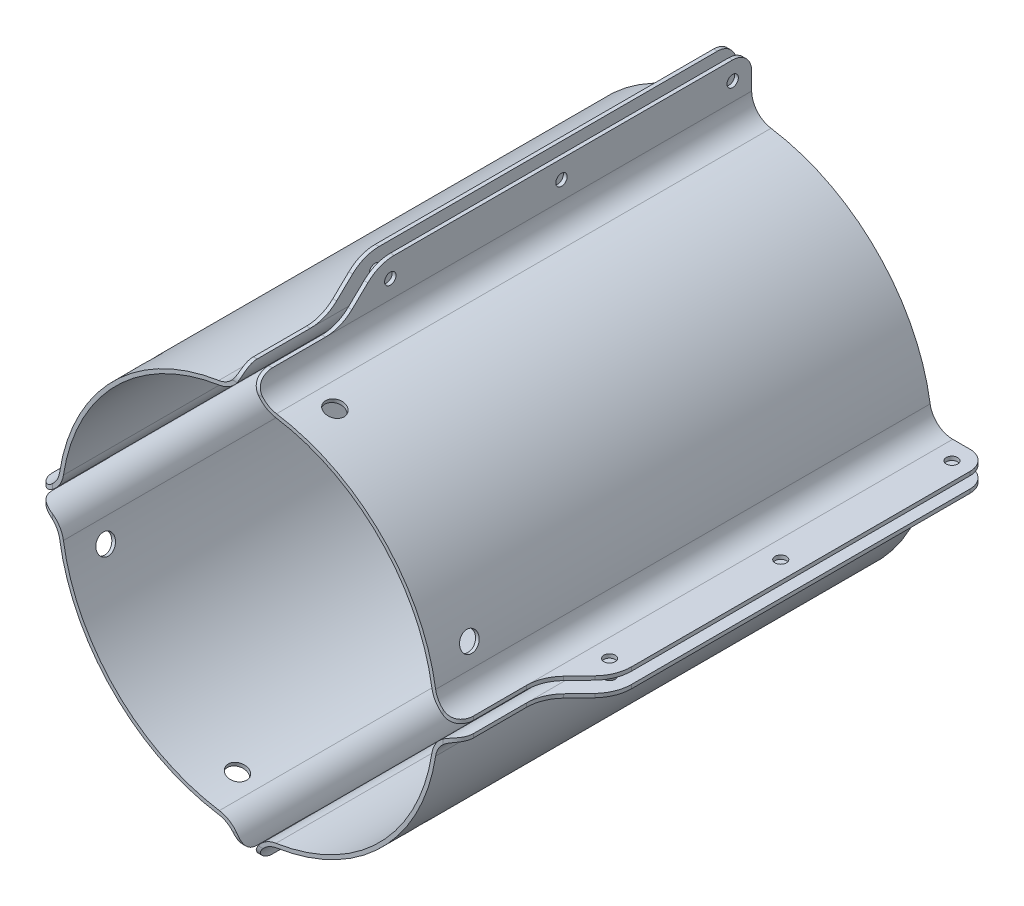
SolidWorks part; units mm, degrees
ref_plane "Спереди" through (0, 0, 0) normal (0, 0, 1) x (1, 0, 0)
ref_plane "Сверху" through (0, 0, 0) normal (0, 1, 0) x (1, 0, 0)
ref_plane "Справа" through (0, 0, 0) normal (1, 0, 0) x (0, 0, -1)
sketch "Эскиз1" plane through (0, 0, 0) normal (0, 0, 1) x (1, 0, 0)
  line L0 (0, 0) -> (0, 63.1749) construction
  line L1 (2.5, 55.3512) -> (2.5, 64.9375)
  line L2 (1.5, 64.9375) -> (1.5, 55.3512)
  line L3 (1.5, 64.9375) -> (2.5, 64.9375)
  line L4 (-1.5, 64.9375) -> (-2.5, 64.9375)
  line L5 (-1.5, 64.9375) -> (-1.5, 55.3512)
  line L6 (-2.5, 55.3512) -> (-2.5, 64.9375)
  line L7 (55.3512, -2.5) -> (64.9375, -2.5)
  line L8 (64.9375, -1.5) -> (55.3512, -1.5)
  line L9 (64.9375, -1.5) -> (64.9375, -2.5)
  line L10 (64.9375, 1.5) -> (64.9375, 2.5)
  line L11 (64.9375, 1.5) -> (55.3512, 1.5)
  line L12 (55.3512, 2.5) -> (64.9375, 2.5)
  line L13 (-2.5, -55.3512) -> (-2.5, -64.9375)
  line L14 (-1.5, -64.9375) -> (-1.5, -55.3512)
  line L15 (-1.5, -64.9375) -> (-2.5, -64.9375)
  line L16 (1.5, -64.9375) -> (2.5, -64.9375)
  line L17 (1.5, -64.9375) -> (1.5, -55.3512)
  line L18 (2.5, -55.3512) -> (2.5, -64.9375)
  line L19 (-55.3512, 2.5) -> (-64.9375, 2.5)
  line L20 (-64.9375, 1.5) -> (-55.3512, 1.5)
  line L21 (-64.9375, 1.5) -> (-64.9375, 2.5)
  line L22 (-64.9375, -1.5) -> (-64.9375, -2.5)
  line L23 (-64.9375, -1.5) -> (-55.3512, -1.5)
  line L24 (-55.3512, -2.5) -> (-64.9375, -2.5)
  arc A0 (-7.5893, 49.4207) -> (-49.4207, 7.5893) centre (0, 0) ccw
  arc A1 (-7.4375, 48.4323) -> (-48.4323, 7.4375) centre (0, 0) ccw
  arc A2 (-7.5893, 49.4207) -> (-2.5, 55.3512) centre (-8.5, 55.3512) ccw
  arc A3 (-7.4375, 48.4323) -> (-1.5, 55.3512) centre (-8.5, 55.3512) ccw
  arc A4 (7.4375, 48.4323) -> (1.5, 55.3512) centre (8.5, 55.3512) cw
  arc A5 (7.5893, 49.4207) -> (2.5, 55.3512) centre (8.5, 55.3512) cw
  arc A6 (49.4207, 7.5893) -> (55.3512, 2.5) centre (55.3512, 8.5) ccw
  arc A7 (48.4323, 7.4375) -> (55.3512, 1.5) centre (55.3512, 8.5) ccw
  arc A8 (48.4323, -7.4375) -> (55.3512, -1.5) centre (55.3512, -8.5) cw
  arc A9 (49.4207, -7.5893) -> (55.3512, -2.5) centre (55.3512, -8.5) cw
  arc A10 (7.5893, -49.4207) -> (2.5, -55.3512) centre (8.5, -55.3512) ccw
  arc A11 (7.4375, -48.4323) -> (1.5, -55.3512) centre (8.5, -55.3512) ccw
  arc A12 (-7.4375, -48.4323) -> (-1.5, -55.3512) centre (-8.5, -55.3512) cw
  arc A13 (-7.5893, -49.4207) -> (-2.5, -55.3512) centre (-8.5, -55.3512) cw
  arc A14 (-49.4207, -7.5893) -> (-55.3512, -2.5) centre (-55.3512, -8.5) ccw
  arc A15 (-48.4323, -7.4375) -> (-55.3512, -1.5) centre (-55.3512, -8.5) ccw
  arc A16 (-48.4323, 7.4375) -> (-55.3512, 1.5) centre (-55.3512, 8.5) cw
  arc A17 (-49.4207, 7.5893) -> (-55.3512, 2.5) centre (-55.3512, 8.5) cw
  arc A18 (-49.4207, -7.5893) -> (-7.5893, -49.4207) centre (0, 0) ccw
  arc A19 (-48.4323, -7.4375) -> (-7.4375, -48.4323) centre (0, 0) ccw
  arc A20 (7.4375, -48.4323) -> (48.4323, -7.4375) centre (0, 0) ccw
  arc A21 (7.5893, -49.4207) -> (49.4207, -7.5893) centre (0, 0) ccw
  arc A22 (49.4207, 7.5893) -> (7.5893, 49.4207) centre (0, 0) ccw
  arc A23 (48.4323, 7.4375) -> (7.4375, 48.4323) centre (0, 0) ccw
  point P13 (-2.5, 49.9375)
  point P16 (-1.5, 48.977)
  point P19 (1.5, 48.977)
  point P22 (2.5, 49.9375)
  point P74 (0, 0)
  dimension "D1" = 100
  dimension "D6" = 6
  dimension "D7" = 7
  dimension "D8" = 7
  dimension "D9" = 6
  dimension "D2" = 1
  dimension "D3" = 15
  dimension "D4" = 5
  dimension "D5" = 1
  dimension "D10" = 4
extrude "Бобышка-Вытянуть1" add sketch "Эскиз1" along normal blind 130
sketch "Эскиз2" plane through (2.5, 0, 0) normal (1, 0, 0) x (0, 0, -1)
  line L1 (0, 55.3512) -> (0, 64.9375) construction
  line L2 (-130, 64.9375) -> (-98, 64.9375)
  line L3 (-130, 64.9375) -> (0, 64.9375) construction
  line L4 (-98, 64.9375) -> (-108, 55.3512)
  line L5 (-130, 55.3512) -> (0, 55.3512) construction
  line L6 (-108, 55.3512) -> (-130, 55.3512)
  line L7 (-130, 64.9375) -> (-130, 55.3512)
  circle A0 centre (-5, 60.1443) radius 1.5
  circle A1 centre (-50, 60.1443) radius 1.5
  circle A2 centre (-95, 60.1443) radius 1.5
  point P12 (0, 60.1443)
  dimension "D3" = 3
  dimension "D1" = 45
  dimension "D2" = 45
  dimension "D4" = 5
  dimension "D5" = 13
  dimension "D6" = 3
extrude "Вырез-Вытянуть1" cut sketch "Эскиз2" against normal blind 130
fillet "Скругление1" radius 4 1 edges at (2, 55.3512, 130)
fillet "Скругление2" radius 4 1 edges at (-2, 55.3512, 130)
fillet "Скругление5" radius 10 1 edges at (-2, 64.9375, 98)
fillet "Скругление6" radius 10 1 edges at (2, 64.9375, 98)
fillet "Скругление7" radius 5 1 edges at (-2, 64.9375, 0)
fillet "Скругление8" radius 5 1 edges at (2, 64.9375, 0)
sketch "Эскиз3" plane through (0, 2.5, 0) normal (0, 1, 0) x (1, 0, 0)
  line L0 (-64.9375, -130) -> (-64.9375, -98)
  line L1 (-64.9375, -98) -> (-55.3512, -108)
  line L2 (-55.3512, -108) -> (-55.3512, -130)
  line L3 (-64.9375, -130) -> (-55.3512, -130)
  circle A0 centre (-60.1443, -5) radius 1.5
  circle A1 centre (-60.1443, -50) radius 1.5
  circle A2 centre (-60.1443, -95) radius 1.5
  point P9 (-60.1443, 0)
extrude "Вырез-Вытянуть2" cut sketch "Эскиз3" against normal up to surface (5 mm away)
pattern_circular "Круговой массив6" count 4 over 360 about axis through (0, 0, 130) along (0, 0, -1) of "Вырез-Вытянуть2"
fillet "Скругление9" radius 4 1 edges at (-55.3512, 2, 130)
fillet "Скругление10" radius 10 2 edges at (-64.9375, 2, 98) (-55.3512, 2, 108)
fillet "Скругление11" radius 5 1 edges at (-64.9375, 2, 0)
fillet "Скругление12" radius 5 2 edges at (-64.9375, -2, 0) (-2, -64.9375, 0)
fillet "Скругление13" radius 4 2 edges at (-2, -55.3512, 130) (-55.3512, -2, 130)
fillet "Скругление14" radius 10 4 edges at (-55.3512, -2, 108) (-64.9375, -2, 98) (-2, -64.9375, 98) (-2, -55.3512, 108)
fillet "Скругление15" radius 5 2 edges at (64.9375, -2, 0) (2, -64.9375, 0)
fillet "Скругление16" radius 5 1 edges at (64.9375, 2, 0)
fillet "Скругление17" radius 10 3 edges at (2, 55.3512, 108) (55.3512, 2, 108) (64.9375, 2, 98)
fillet "Скругление18" radius 10 1 edges at (-2, 55.3512, 108)
fillet "Скругление19" radius 4 1 edges at (55.3512, 2, 130)
fillet "Скругление20" radius 10 4 edges at (55.3512, -2, 108) (64.9375, -2, 98) (2, -55.3512, 108) (2, -64.9375, 98)
fillet "Скругление21" radius 4 2 edges at (2, -55.3512, 130) (55.3512, -2, 130)
ref_plane "Плоскость1" through (0, 0, 0) normal (-0.7071, 0.7071, 0) x (0.7071, 0.7071, 0)
sketch "Эскиз4" plane through (0, 0, 0) normal (-0.7071, 0.7071, 0) x (0.7071, 0.7071, 0)
  line L0 (-29.5793, -130) -> (29.5793, -130) construction
  circle A0 centre (0, -120) radius 2.5
  dimension "D1" = 5
  dimension "D2" = 10
extrude "Вырез-Вытянуть3" cut sketch "Эскиз4" against normal through all
pattern_circular "Круговой массив7" count 6 over 360 about axis through (0, 0, 130) along (0, 0, -1) of "Вырез-Вытянуть3"
equation "\"D5@Эскиз1\"=\"D2@Эскиз1\""
